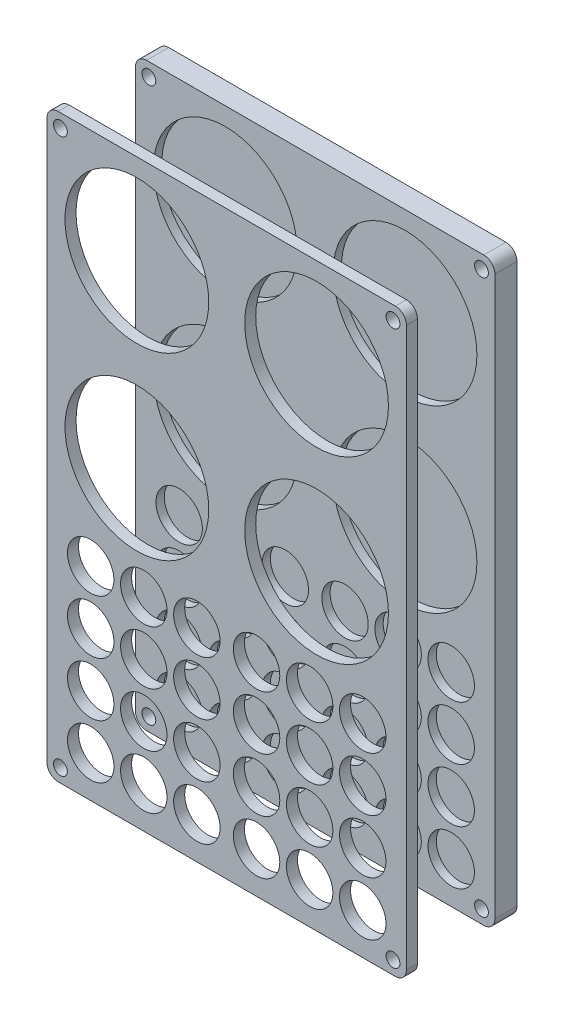
SolidWorks part; units mm, degrees
ref_plane "Front Plane" through (0, 0, 0) normal (1, 0, 0) x (0, 1, 0)
ref_plane "Top Plane" through (0, 0, 0) normal (0, 0, 1) x (0, 1, 0)
ref_plane "Right Plane" through (0, 0, 0) normal (0, 1, 0) x (-1, 0, 0)
sketch "Sketch1" plane through (0, 0, 0) normal (0, 0, 1) x (0, 1, 0)
  line L1 (-105, -65) -> (105, -65)
  line L2 (-105, -65) -> (-105, 65)
  line L3 (-105, 65) -> (105, 65)
  line L4 (105, -65) -> (105, 65)
  line L5 (-105, -65) -> (105, 65) construction
  line L6 (-105, 65) -> (105, -65) construction
  point P0 (0, 0)
  dimension "D1" = 130
  dimension "D2" = 210
extrude "120 x 200 x 67 th" add sketch "Sketch1" along normal blind 40
sketch "Sketch2" plane through (0, 0, 40) normal (0, 0, 1) x (1, 0, 0)
  line L0 (-65, 0) -> (65, 0) construction
  line L1 (-65, 105) -> (-65, -105) construction
  line L2 (65, -105) -> (65, 105) construction
  line L3 (0, 105) -> (0, -105) construction
  line L4 (65, 105) -> (-65, 105) construction
  line L5 (-65, -105) -> (65, -105) construction
  line L6 (-65, 72.5) -> (-58.5, 72.5)
  line L7 (-32.5, 105) -> (-32.5, 98.5)
  line L8 (-6.5, 72.5) -> (0, 72.5)
  line L9 (-65, 40) -> (65, 40) construction
  line L10 (-32.5, 46.5) -> (-32.5, 40)
  line L11 (-62.6582, -100.1582) -> (-65, -100.1582)
  line L12 (-60.1582, -102.6582) -> (-60.1582, -105)
  circle A0 centre (-32.5, 72.5) radius 26
  circle A2 centre (-49.2, -12.1416) radius 8.4 construction
  circle A32 centre (-30, -12.1416) radius 8.4 construction
  circle A33 centre (-10.8, -12.1416) radius 8.4 construction
  circle A34 centre (10.8, -12.1416) radius 8.4 construction
  circle A35 centre (30, -12.1416) radius 8.4 construction
  circle A36 centre (49.2, -12.1416) radius 8.4 construction
  circle A37 centre (10.8, -31.6416) radius 8.4
  circle A38 centre (30, -31.6416) radius 8.4
  circle A39 centre (49.2, -31.6416) radius 8.4
  circle A40 centre (-10.8, -31.6416) radius 8.4
  circle A41 centre (-30, -31.6416) radius 8.4
  circle A42 centre (-49.2, -31.6416) radius 8.4
  circle A43 centre (10.8, -51.1416) radius 8.4
  circle A44 centre (30, -51.1416) radius 8.4
  circle A45 centre (49.2, -51.1416) radius 8.4
  circle A46 centre (-10.8, -51.1416) radius 8.4
  circle A47 centre (-30, -51.1416) radius 8.4
  circle A48 centre (-49.2, -51.1416) radius 8.4
  circle A49 centre (10.8, -70.6416) radius 8.4
  circle A50 centre (30, -70.6416) radius 8.4
  circle A51 centre (49.2, -70.6416) radius 8.4
  circle A52 centre (-10.8, -70.6416) radius 8.4
  circle A53 centre (-30, -70.6416) radius 8.4
  circle A54 centre (-49.2, -70.6416) radius 8.4
  circle A55 centre (10.8, -90.1416) radius 8.4
  circle A56 centre (30, -90.1416) radius 8.4
  circle A57 centre (49.2, -90.1416) radius 8.4
  circle A58 centre (-10.8, -90.1416) radius 8.4
  circle A59 centre (-30, -90.1416) radius 8.4
  circle A60 centre (-49.2, -90.1416) radius 8.4
  circle A61 centre (32.5, 72.5) radius 26
  circle A64 centre (32.5, 7.5) radius 26
  circle A65 centre (-32.5, 7.5) radius 26
  circle A66 centre (-60.1582, -100.1582) radius 2.5
  circle A67 centre (-60.1582, 100.1582) radius 2.5
  circle A68 centre (60.1582, -100.1582) radius 2.5
  circle A69 centre (60.1582, 100.1582) radius 2.5
  point P35 (-32.5, 53)
  dimension "D1" = 52
  dimension "D2" = 3
  dimension "D4" = 5
  dimension "D3" = 5
extrude "16.8 D and 52 D tube holes" cut sketch "Sketch2" against normal blind 35 contours A0 | A61 | A2 | A32 | A33 | A34 | A35 | A36 | A42 | A41 | A40 | A37 | A38 | A39 | A48 | A47 | A46 | A43 | A44 | A45 | A54 | A53 | A52 | A49 | A50 | A51 | A60 | A59 | A58 | A55 | A56 | A57 | A65 | A64 region at (-32.5, 72.5, 40) region at (10.8, -31.6416, 40) region at (30, -31.6416, 40) region at (49.2, -31.6416, 40) region at (-10.8, -31.6416, 40) region at (-30, -31.6416, 40) region at (-49.2, -31.6416, 40) region at (10.8, -51.1416, 40) region at (30, -51.1416, 40) region at (49.2, -51.1416, 40) region at (-10.8, -51.1416, 40) region at (-30, -51.1416, 40) region at (-49.2, -51.1416, 40) region at (10.8, -70.6416, 40) region at (30, -70.6416, 40) region at (49.2, -70.6416, 40) region at (-10.8, -70.6416, 40) region at (-30, -70.6416, 40) region at (-49.2, -70.6416, 40) region at (10.8, -90.1416, 40) region at (30, -90.1416, 40) region at (49.2, -90.1416, 40) region at (-10.8, -90.1416, 40) region at (-30, -90.1416, 40) region at (-49.2, -90.1416, 40) region at (32.5, 72.5, 40) region at (32.5, 7.5, 40) region at (-32.5, 7.5, 40)
fillet "4 mm R filet" radius 4 4 edges at (-65, 105, 20) (65, 105, 20) (-65, -105, 20) (65, -105, 20)
sketch "Sketch3" plane through (0, 0, 0) normal (1, 0, 0) x (0, 1, 0)
  line L0 (-105, 0) -> (-105, 8) construction
  line L1 (-105, 40) -> (-105, 36)
  line L2 (-105, 0) -> (-105, 40) construction
  line L3 (105, 40) -> (105, 0) construction
  line L4 (-105, 8) -> (105, 8)
  line L5 (-105, 8) -> (-105, 36)
  line L6 (-105, 36) -> (105, 36)
  line L7 (105, 8) -> (105, 36)
  line L8 (-105, 8) -> (105, 36) construction
  line L9 (-105, 36) -> (105, 8) construction
  point P11 (0, 22)
  point P14 (0, 0)
  dimension "D1" = 8
  dimension "D2" = 4
extrude "Cut-Extrude1" cut sketch "Sketch3" against normal through all both and the other way through all contours L4 L7 L6 L5 region at (0, 0, 22)
extrude "Cut-Extrude2" cut sketch "Sketch2<3>" against normal through all both and the other way through all contours A66 | A68 | A67 | A69 region at (-60.1582, -100.1582, 40) region at (-60.1582, 100.1582, 40) region at (60.1582, -100.1582, 40) region at (60.1582, 100.1582, 40)
sketch "Sketch2<3>" plane through (0, 0, 40) normal (0, 0, 1) x (1, 0, 0) same geometry as "Sketch2"
